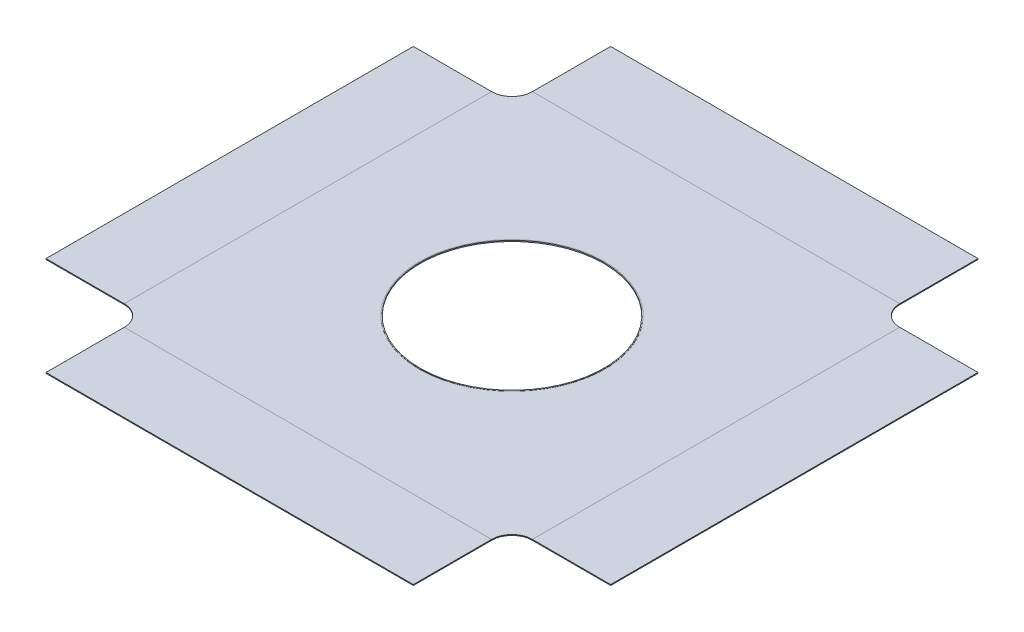
SolidWorks part; units mm, degrees
material "7050-T73510"
ref_plane "Front Plane" through (0, 0, 0) normal (0, 0, 1) x (1, 0, 0)
ref_plane "Top Plane" through (0, 0, 0) normal (0, 1, 0) x (1, 0, 0)
ref_plane "Right Plane" through (0, 0, 0) normal (1, 0, 0) x (0, 0, -1)
sketch "Sketch1" plane through (0, 0, 0) normal (0, 1, 0) x (1, 0, 0)
  line L1 (-171.45, -171.45) -> (171.45, -171.45)
  line L2 (-171.45, -171.45) -> (-171.45, 171.45)
  line L3 (-171.45, 171.45) -> (171.45, 171.45)
  line L4 (171.45, -171.45) -> (171.45, 171.45)
  line L5 (-171.45, -171.45) -> (171.45, 171.45) construction
  line L6 (-171.45, 171.45) -> (171.45, -171.45) construction
  point P0 (0, 0)
  dimension "D1" = 342.9
extrude "Boss-Extrude1" add sketch "Sketch1" along normal mid plane 0.8128 contours L3 L4 L1 L2
sketch "Sketch2" plane through (0, 0.4064, 0) normal (0, 1, 0) x (1, 0, 0)
  circle A0 centre (0, 0) radius 85.725
  dimension "D1" = 171.45
sketch "Sketch4" plane through (-171.45, 0, 0) normal (-1, 0, 0) x (0, 0, 1)
  line L4 (-171.45, -0.4064) -> (171.45, -0.4064)
  line L5 (171.45, -0.4064) -> (171.45, 0.4064)
  line L6 (171.45, 0.4064) -> (-171.45, 0.4064)
  line L7 (-171.45, 0.4064) -> (-171.45, -0.4064)
  line L8 (-171.45, -0.4064) -> (171.45, -0.4064)
  line L9 (171.45, -0.4064) -> (171.45, 0.4064)
  line L10 (171.45, 0.4064) -> (-171.45, 0.4064)
  line L11 (-171.45, 0.4064) -> (-171.45, -0.4064)
  dimension "D1" = 0
extrude "Boss-Extrude3" add sketch "Sketch4" along normal blind 92.075
ref_axis "Axis1" through (0, 2.794, 0) along (0, -1, 0)
pattern_circular "CirPattern1" count 4 over 360 about axis through (0, 2.794, 0) along (0, -1, 0) of "Boss-Extrude3"
fillet "Fillet1" radius 19.05 4 edges at (-171.45, 0, -171.45) (-171.45, 0, 171.45) (171.45, 0, 171.45) (171.45, 0, -171.45)
ref_plane "Plane1" through (-190.5, 0, 0) normal (-1, 0, 0) x (0, 0, 1)
split line "Split Line1"
ref_plane "Plane2" through (0, 0, -190.5) normal (0, 0, -1) x (-1, 0, 0)
split line "Split Line2"
ref_plane "Plane3" through (190.5, 0, 0) normal (1, 0, 0) x (0, 0, -1)
split line "Split Line3"
ref_plane "Plane4" through (0, 0, 190.5) normal (0, 0, 1) x (1, 0, 0)
split line "Split Line4"
sketch "Sketch7" plane through (0, 0.4064, 0) normal (0, 1, 0) x (1, 0, 0)
  circle A0 centre (0, 0) radius 86.5823
  circle A1 centre (0, 0) radius 85.725
  dimension "D1" = 171.45
  dimension "D2" = 0.8573
extrude "Cut-Extrude1" cut sketch "Sketch7" against normal blind 88.9 contours A1
extrude "Boss-Extrude4" add sketch "Sketch7<3>" along normal mid plane 0.4064
sketch "Sketch7<3>" plane through (0, 0.4064, 0) normal (0, 1, 0) x (1, 0, 0) same geometry as "Sketch7"
equation "\"b\"= 15 - 1.5'Width of plate"
equation "\"D1@Sketch1\"=\"b\""
equation "\"t\"= .032'Thickness of sheet"
equation "\"d\"= \"b\" / 2'Diameter of hole"
equation "\"w\"= \"d\" / 200'Width of hole"
equation "\"D1@Boss-Extrude1\"=\"t\""
equation "\"D1@Sketch2\"=\"d\""
equation "\"h\"= \"t\" * 1'Thickness of hole"
equation "\"x\"= 3.625'Extra plates..."
equation "\"D1@Boss-Extrude3\"=\"x\""
equation "\"D2@Sketch7\"=\"w\""
equation "\"D1@Boss-Extrude4\"=\"h\"/2"
equation "\"D1@Sketch7\"=\"d\""
